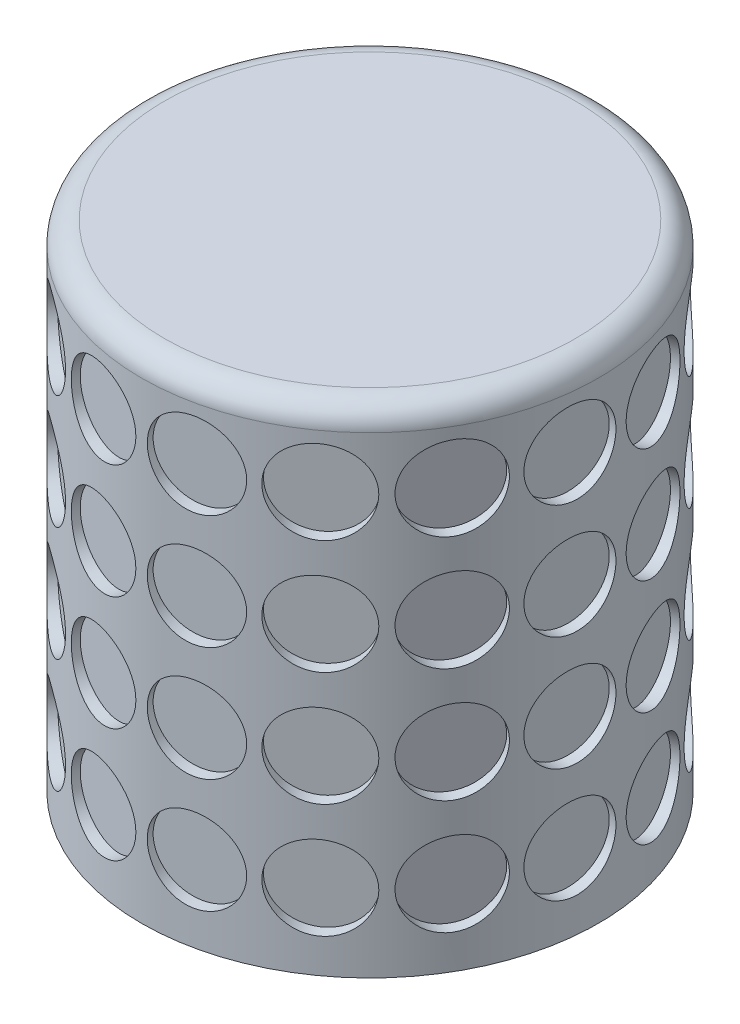
SolidWorks part; units mm, degrees
ref_plane "Plan de face" through (0, 0, 0) normal (1, 0, 0) x (0, 1, 0)
ref_plane "Plan de dessus" through (0, 0, 0) normal (0, 0, 1) x (0, 1, 0)
ref_plane "Plan de droite" through (0, 0, 0) normal (0, 1, 0) x (-1, 0, 0)
sketch "Esquisse1" plane through (0, 0, 0) normal (0, 0, 1) x (0, 1, 0)
  line L0 (56.3846, 24.5) -> (3.2137, 24.5) construction
  line L1 (-8.6154, 54.5) -> (46.3846, 54.5)
  line L2 (-8.6154, 54.5) -> (-8.6154, 47)
  line L3 (-8.6154, 47) -> (46.3846, 47)
  line L4 (46.3846, 54.5) -> (46.3846, 47)
  line L5 (46.3846, 54.5) -> (56.3846, 54.5)
  line L6 (46.3846, 54.5) -> (46.3846, -5.5)
  line L7 (46.3846, -5.5) -> (56.3846, -5.5)
  line L8 (56.3846, 54.5) -> (56.3846, -5.5)
  line L9 (46.3846, -5.5) -> (-8.6154, -5.5)
  line L10 (46.3846, -5.5) -> (46.3846, 2)
  line L11 (46.3846, 2) -> (-8.6154, 2)
  line L12 (-8.6154, -5.5) -> (-8.6154, 2)
  dimension "D1" = 10
  dimension "D2" = 7.5
  dimension "D3" = 7.5
  dimension "D4" = 45
  dimension "D5" = 55
  dimension "D6" = 55
revolve "Révolution1" add sketch "Esquisse1" angle 360 about L0 region at (-9.5, 51.3846, 0) region at (1.75, 18.8846, 0)
sketch "Esquisse3" plane through (0, 56.3846, 0) normal (0, 1, 0) x (-1, 0, 0)
  line L0 (24.5, 0) -> (24.5, -30)
  line L1 (24.5, 0) -> (29.7094, -29.5442)
  circle A0 centre (24.5, 0) radius 30 construction
  dimension "D1" = 10
ref_plane "Plan1" through (-24.5, 56.3846, -30) normal (0, 0, -1) x (-1, 0, 0)
fillet "Congé1" radius 3 1 edges at (-24.5, 56.3846, 30)
sketch "Esquisse4" plane through (-24.5, 56.3846, -30) normal (0, 0, -1) x (-1, 0, 0)
  line L0 (-30, -65) -> (30, -65) construction
  circle A0 centre (0, -10) radius 5.5
  circle A1 centre (0, -25) radius 5.5
  circle A2 centre (0, -40) radius 5.5
  circle A3 centre (0, -55) radius 5.5
  dimension "D1" = 11
  dimension "D2" = 11
  dimension "D3" = 11
  dimension "D4" = 11
  dimension "D5" = 15
  dimension "D6" = 15
  dimension "D7" = 0
  dimension "D8" = 15
  dimension "D9" = 10
  dimension "D10" = 0
  dimension "D11" = 0
  dimension "D12" = 0
extrude "Enlèv. mat.-Extru.1" cut sketch "Esquisse4" against normal blind 1.5
pattern_circular "Répétition circulaire1" count 15 every 24 about axis through (-24.5, 56.3846, 0) along (0, 1, 0) of "Enlèv. mat.-Extru.1"
sketch "Esquisse5" plane through (0, 46.3846, 0) normal (0, -1, 0) x (1, 0, 0)
  circle A0 centre (-24.5, 0) radius 6.5
  circle A1 centre (-24.5, 0) radius 4.75
  dimension "D1" = 9.5
  dimension "D2" = 13
extrude "Boss.-Extru.1" add sketch "Esquisse5" along normal blind 20
fillet "Congé2" radius 10 1 edges at (-24.5, 46.3846, 6.5)
